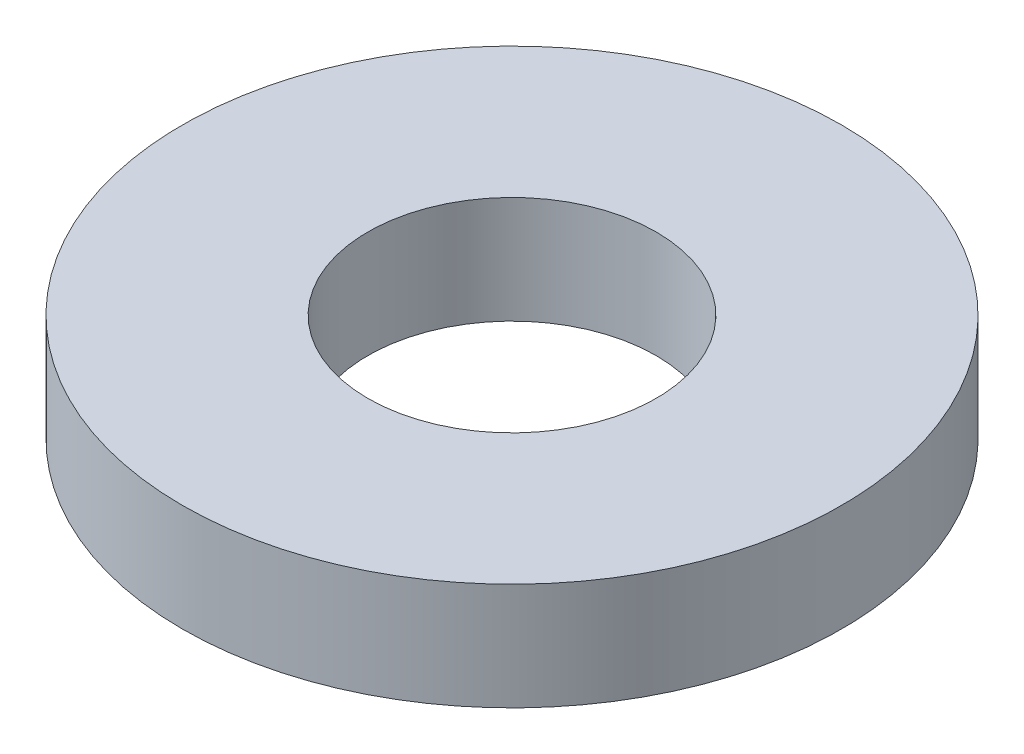
SolidWorks part; units mm, degrees
ref_plane "Front Plane" through (0, 0, 0) normal (0, 0, 1) x (1, 0, 0)
ref_plane "Top Plane" through (0, 0, 0) normal (0, 1, 0) x (1, 0, 0)
ref_plane "Right Plane" through (0, 0, 0) normal (1, 0, 0) x (0, 0, -1)
sketch "Sketch1" plane through (0, 0, 0) normal (0, 1, 0) x (1, 0, 0)
  circle A0 centre (0, 0) radius 40
  dimension "FLANGE_OD" = 80
extrude "Boss-Extrude1" add sketch "Sketch1" along normal blind 13
sketch "Sketch2" plane through (0, 0, 0) normal (0, 1, 0) x (1, 0, 0)
  circle A0 centre (0, 0) radius 17.5
  dimension "BORE_D" = 35
extrude "Cut-Extrude1" cut sketch "Sketch2" along normal through all
sketch "Sketch3" plane through (0, 13, 0) normal (0, 1, 0) x (1, 0, 0)
  circle A0 centre (0, 0) radius 13.454 construction
  circle A1 centre (-13.454, 0) radius 3.9726
  dimension "BOLT_D" = 7.9452
  dimension "BOLT_PCD" = 26.908
extrude "Cut-Extrude2" cut sketch "Sketch3" against normal blind 12.4155 rebuild error yes
pattern_circular "CirPattern1" count 4 over 360 rebuild error yes
